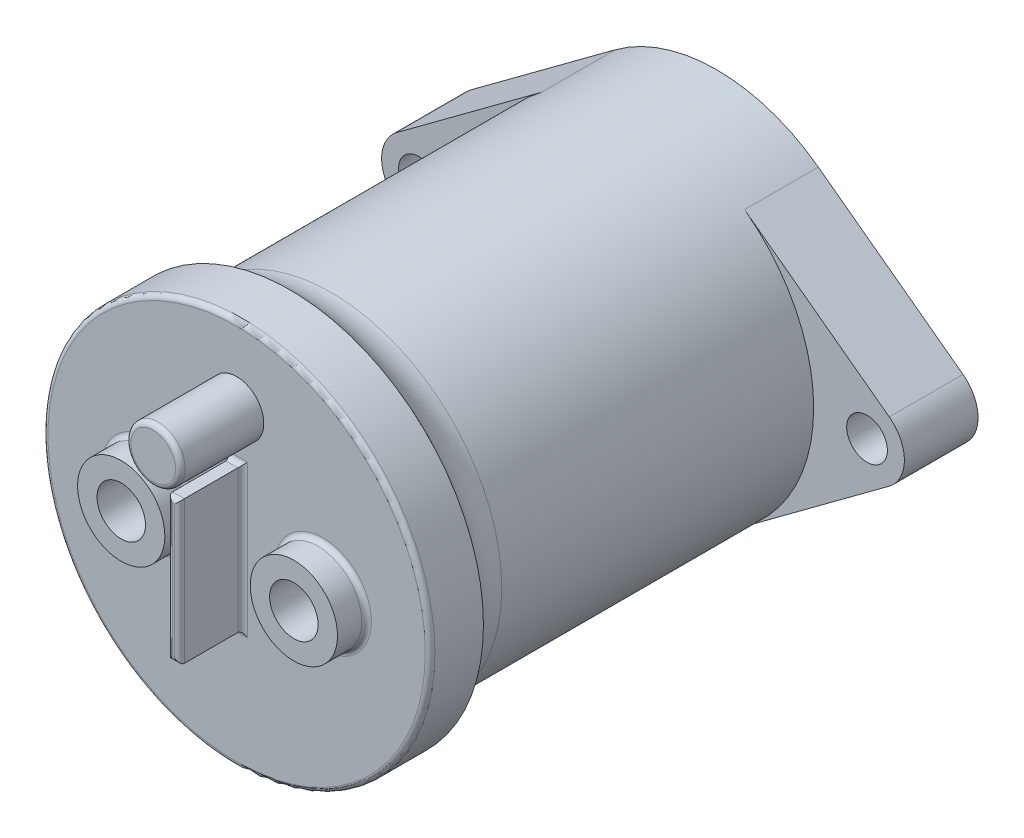
SolidWorks part; units mm, degrees
material "Custom Plastic"
ref_plane "X-Y Datum" through (0, 0, 0) normal (0, 0, 1) x (1, 0, 0)
ref_plane "X-Z Datum" through (0, 0, 0) normal (0, 1, 0) x (1, 0, 0)
ref_plane "Y-Z Datum" through (0, 0, 0) normal (1, 0, 0) x (0, 0, -1)
sketch "Sketch2" plane through (0, 0, 0) normal (0, 0, 1) x (1, 0, 0)
  circle A0 centre (0, 0) radius 17.6
  dimension "D1" = 35.2
extrude "Boss-Extrude1" add sketch "Sketch2" along normal blind 52.5
sketch "Sketch3" plane through (0, 0, 0) normal (0, 0, 1) x (1, 0, 0)
  line L0 (-23.1, 0) -> (23.1, 0) construction
  line L1 (-26.95, 0) -> (26.95, 0) construction
  line L2 (-25.3917, 3.0937) -> (-10.4762, 14.1425)
  line L3 (-25.3917, -3.0937) -> (-10.4762, -14.1425)
  line L4 (0, 28.5555) -> (0, -28.5555) construction
  line L5 (25.3917, -3.0937) -> (10.4762, -14.1425)
  line L6 (25.3917, 3.0937) -> (10.4762, 14.1425)
  circle A0 centre (23.1, 0) radius 2.1
  circle A1 centre (-23.1, 0) radius 2.1
  circle A2 centre (23.1, 0) radius 3.85
  circle A3 centre (-23.1, 0) radius 3.85
  circle A6 centre (0, 0) radius 17.6 construction
  circle A8 centre (0, 0) radius 17.6
  circle A9 centre (0, 0) radius 17.6
  point P4 (0, 0)
  point P10 (0, 0)
  point P23 (0, 0)
  dimension "D2" = 4.2
  dimension "D1" = 46.2
  dimension "D3" = 53.9
  dimension "D4" = 0
extrude "Boss-Extrude2" add sketch "Sketch3" along normal blind 7.6 contours A9 A2 L6 | A9 L5 A2 | A9 A2 A0 | A9 A3 A1 | A9 A3 L3 | A9 L2 A3 region at (-18.5342, 0, 0) region at (-21.417, 3.3412, 0) region at (18.5342, 0, 0) region at (26.4412, 1.683, 0)
sketch "Sketch4" plane through (0, 0, 52.5) normal (0, 0, 1) x (1, 0, 0)
  line L0 (-8.9, 0) -> (8.9, 0) construction
  line L1 (-0.615, 7.35) -> (0.615, 7.35)
  line L2 (-0.615, 7.35) -> (-0.615, -7.35)
  line L3 (-0.615, -7.35) -> (0.615, -7.35)
  line L4 (0.615, 7.35) -> (0.615, -7.35)
  line L5 (-0.615, 7.35) -> (0.615, -7.35) construction
  line L6 (-0.615, -7.35) -> (0.615, 7.35) construction
  circle A0 centre (-8.9, 0) radius 2.5
  circle A1 centre (8.9, 0) radius 2.5
  circle A2 centre (-8.9, 0) radius 4.5
  circle A3 centre (8.9, 0) radius 4.5
  point P0 (0, 0)
  point P11 (0, 0)
  dimension "D4" = 5
  dimension "D5" = 9
  dimension "D1" = 1.23
  dimension "D2" = 14.7
  dimension "D3" = 17.8
extrude "Boss-Extrude3" add sketch "Sketch4" along normal blind 3.5 contours L2 L1 L4 L3
sketch "Sketch5" plane through (0, 0, 52.5) normal (0, 0, 1) x (1, 0, 0)
  line L4 (0.615, 7.35) -> (-0.615, 7.35)
  line L5 (0.615, -7.35) -> (0.615, 7.35)
  line L6 (-0.615, -7.35) -> (0.615, -7.35)
  line L7 (-0.615, 7.35) -> (-0.615, -7.35)
  line L8 (0.615, 7.35) -> (-0.615, 7.35)
  line L9 (0.615, -7.35) -> (0.615, 7.35)
  line L10 (-0.615, -7.35) -> (0.615, -7.35)
  line L11 (-0.615, 7.35) -> (-0.615, -7.35)
  circle A1 centre (8.9, 0) radius 4.5
  circle A2 centre (8.9, 0) radius 4.5
  circle A3 centre (-8.9, 0) radius 4.5
  circle A4 centre (-8.9, 0) radius 4.5
  circle A5 centre (8.9, 0) radius 2.5
  circle A6 centre (8.9, 0) radius 2.5
  circle A7 centre (-8.9, 0) radius 2.5
  circle A8 centre (-8.9, 0) radius 2.5
  circle M22 centre (0, 0) radius 17.6
  line M23 (0.615, 7.35) -> (0.615, -7.35)
  line M24 (0.615, -7.35) -> (-0.615, -7.35)
  line M25 (-0.615, -7.35) -> (-0.615, 7.35)
  line M26 (-0.615, 7.35) -> (0.615, 7.35)
  dimension "D1" = 0
  dimension "D2" = 0
  dimension "D3" = 0
  dimension "D4" = 0
  dimension "D5" = 0
extrude "Cut-Extrude1" cut sketch "Sketch5" against normal blind 3 contours A4 A2 M22 M26 M23 M24 M25 | A8 | A6 region at (8.9, 0, 52.5) region at (-8.9, 0, 52.5) region at (-17.1022, 0, 52.5)
sketch "Sketch7" plane through (0, 0, 49.5) normal (0, 0, 1) x (1, 0, 0)
  circle A0 centre (0, 0) radius 19.95
  dimension "D1" = 39.9
extrude "Boss-Extrude5" add sketch "Sketch7" against normal blind 5.5
fillet "Fillet3" radius 5 1 edges at (17.6, 0, 44)
fillet "Fillet4" radius 0.5 11 edges at (-0.615, 0, 56) (0, 7.35, 56) (0.615, 0, 56) (0, -7.35, 56) (19.95, 0, 49.5) (-0.615, 0, 49.5) (0, -7.35, 49.5) (0.615, 0, 49.5) (0, 7.35, 49.5) (13.4, 0, 49.5) (-4.4, 0, 49.5)
sketch "Sketch8" plane through (0, 0, 52.5) normal (0, 0, 1) x (1, 0, 0)
  circle A0 centre (-8.9, 0) radius 2.5 construction
  circle A1 centre (8.9, 0) radius 2.5
  circle A2 centre (8.9, 0) radius 2.5
  circle A3 centre (-8.9, 0) radius 2.5
  dimension "D1" = 0
extrude "Cut-Extrude2" cut sketch "Sketch8" against normal blind 7
sketch "Sketch10" plane through (0, 0, 49.5) normal (0, 0, 1) x (1, 0, 0)
  line L0 (0, 0) -> (0, 12.15) construction
  line L1 (0.615, 7.35) -> (-0.615, 7.35) construction
  circle A0 centre (0, 12.15) radius 2.8
  point P2 (0, 9.35)
  dimension "D1" = 5.6
  dimension "D2" = 2
extrude "Boss-Extrude6" add sketch "Sketch10" along normal blind 8.6
fillet "Fillet5" radius 0.5 1 edges at (2.8, 12.15, 58.1)
ref_plane "Plane3" through (0, 0, 0) normal (0.866, 0.5, 0) x (0, 0, -1)
ref_plane "Plane4" through (0, 0, 0) normal (0.5, -0.866, 0) x (0, 0, -1)
